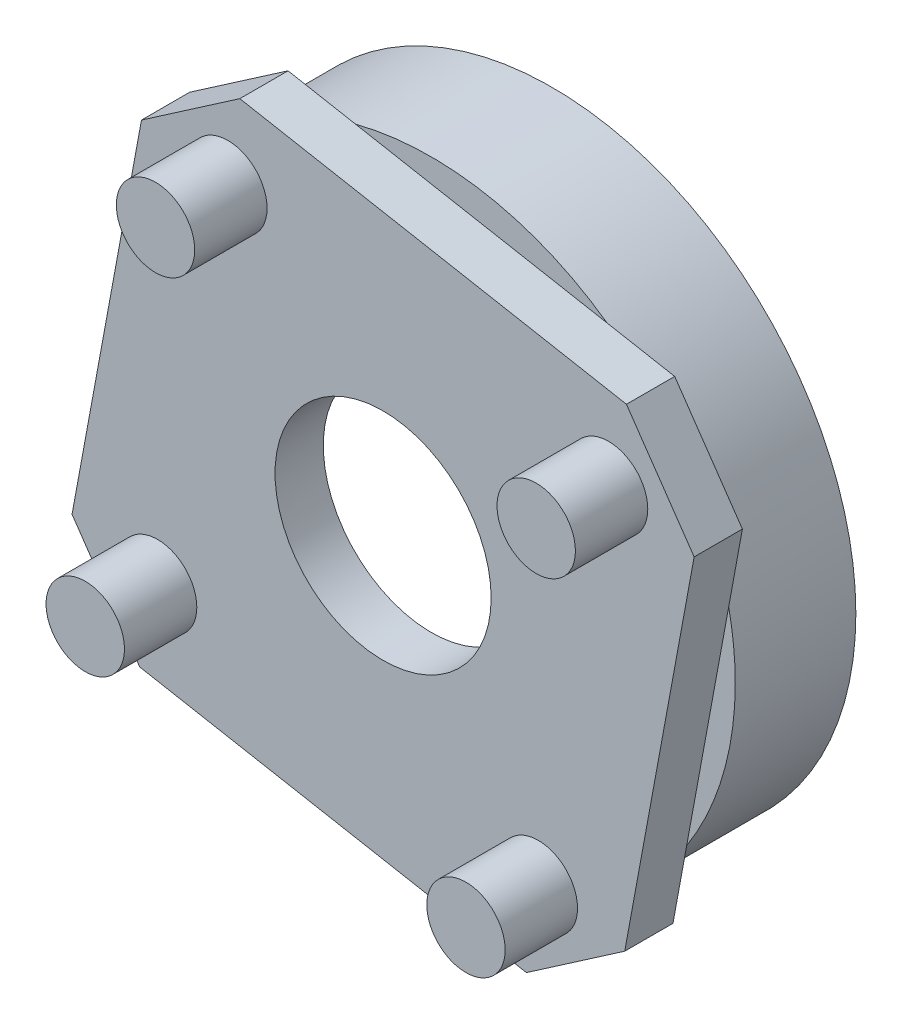
SolidWorks part; units mm, degrees
ref_plane "Front Plane" through (0, 0, 0) normal (0, 0, 1) x (1, 0, 0)
ref_plane "Top Plane" through (0, 0, 0) normal (0, 1, 0) x (1, 0, 0)
ref_plane "Right Plane" through (0, 0, 0) normal (1, 0, 0) x (0, 0, -1)
sketch "Sketch1" plane through (0, 0, 0) normal (0, 0, 1) x (1, 0, 0)
  circle A1 centre (0, 0) radius 12.6
  circle A2 centre (0, 0) radius 11.1
  circle A3 centre (0, 0) radius 11.1
  dimension "D1" = 0.1
  dimension "D2" = 1.5
extrude "Boss-Extrude1" add sketch "Sketch1" against normal blind 5
chamfer "Chamfer1" distance 1 angle 45 1 edges at (11.1, 0, -5)
sketch "Sketch2" plane through (0, 0, 0) normal (0, 0, 1) x (1, 0, 0)
  circle A0 centre (-6.4355, 9.348) radius 1.775 construction
  circle A1 centre (9.348, 6.4355) radius 1.775 construction
  circle A2 centre (6.4355, -9.348) radius 1.775 construction
  circle A3 centre (-9.348, -6.4355) radius 1.775 construction
  circle A4 centre (-6.4355, 9.348) radius 1.775 construction
  circle A6 centre (9.348, 6.4355) radius 1.775 construction
  circle A7 centre (6.4355, -9.348) radius 1.775 construction
  circle A8 centre (-9.348, -6.4355) radius 1.775 construction
  circle A9 centre (-9.348, -6.4355) radius 1.625
  circle A10 centre (6.4355, -9.348) radius 1.625
  circle A11 centre (9.348, 6.4355) radius 1.625
  circle A12 centre (-6.4355, 9.348) radius 1.625
  dimension "D1" = 0.15
extrude "Boss-Extrude2" add sketch "Sketch2" along normal blind 5
sketch "Sketch3" plane through (0, 0, 0) normal (0, 0, 1) x (1, 0, 0)
  line L0 (12.8956, 5.6843) -> (10.0888, 9.7613)
  line L1 (5.9406, -12.7191) -> (10.0176, -9.9124)
  line L2 (-12.8956, -5.6843) -> (-10.0888, -9.7613)
  line L3 (-5.9406, 12.7191) -> (-10.0176, 9.9124)
  line L5 (-10.5805, -9.6706) -> (6.4323, -12.8099)
  line L6 (9.9269, -10.4041) -> (12.9863, 6.176)
  line L7 (10.5805, 9.6706) -> (-6.4323, 12.8099)
  line L8 (-9.9269, 10.4041) -> (-12.9863, -6.176)
  line L9 (-10.0888, -9.7613) -> (5.9406, -12.7191)
  line L10 (10.0176, -9.9124) -> (12.8956, 5.6843)
  line L11 (10.0888, 9.7613) -> (-5.9406, 12.7191)
  line L12 (-10.0176, 9.9124) -> (-12.8956, -5.6843)
  arc A0 (-8.0173, 9.7202) -> (-10.9585, -6.2187) centre (0, 0) ccw construction
  arc A1 (-8.0173, 9.7202) -> (-10.9585, -6.2187) centre (0, 0) ccw
  arc A4 (6.4323, -12.8099) -> (9.9269, -10.4041) centre (6.9767, -9.8597) ccw
  arc A5 (12.9863, 6.176) -> (10.5805, 9.6706) centre (10.0361, 6.7204) ccw
  arc A6 (-6.4323, 12.8099) -> (-9.9269, 10.4041) centre (-6.9767, 9.8597) ccw
  arc A7 (-12.9863, -6.176) -> (-10.5805, -9.6706) centre (-10.0361, -6.7204) ccw
  arc A12 (-9.7202, -8.0173) -> (6.2187, -10.9585) centre (0, 0) ccw
  arc A13 (4.9252, -9.9475) -> (6.2187, -10.9585) centre (6.4355, -9.348) ccw
  arc A14 (-8.151, -7.5346) -> (4.9252, -9.9475) centre (0, 0) ccw
  arc A15 (-9.7202, -8.0173) -> (-8.151, -7.5346) centre (-9.348, -6.4355) ccw
  arc A16 (-9.7202, -8.0173) -> (6.2187, -10.9585) centre (0, 0) ccw
  arc A17 (4.9252, -9.9475) -> (6.2187, -10.9585) centre (6.4355, -9.348) ccw
  arc A18 (-8.151, -7.5346) -> (4.9252, -9.9475) centre (0, 0) ccw
  arc A19 (-9.7202, -8.0173) -> (-8.151, -7.5346) centre (-9.348, -6.4355) ccw
  arc A22 (-7.5346, 8.151) -> (-9.9475, -4.9252) centre (0, 0) ccw
  arc A23 (-8.0173, 9.7202) -> (-7.5346, 8.151) centre (-6.4355, 9.348) ccw
  arc A24 (-8.0173, 9.7202) -> (-10.9585, -6.2187) centre (0, 0) ccw
  arc A25 (-9.9475, -4.9252) -> (-10.9585, -6.2187) centre (-9.348, -6.4355) ccw
  arc A26 (-7.5346, 8.151) -> (-9.9475, -4.9252) centre (0, 0) ccw
  arc A27 (-8.0173, 9.7202) -> (-7.5346, 8.151) centre (-6.4355, 9.348) ccw
  arc A28 (-8.0173, 9.7202) -> (-10.9585, -6.2187) centre (0, 0) ccw
  arc A29 (-9.9475, -4.9252) -> (-10.9585, -6.2187) centre (-9.348, -6.4355) ccw
  arc A30 (9.7202, 8.0173) -> (-6.2187, 10.9585) centre (0, 0) ccw
  arc A31 (-4.9252, 9.9475) -> (-6.2187, 10.9585) centre (-6.4355, 9.348) ccw
  arc A32 (8.151, 7.5346) -> (-4.9252, 9.9475) centre (0, 0) ccw
  arc A33 (9.7202, 8.0173) -> (8.151, 7.5346) centre (9.348, 6.4355) ccw
  arc A34 (9.7202, 8.0173) -> (-6.2187, 10.9585) centre (0, 0) ccw
  arc A35 (-4.9252, 9.9475) -> (-6.2187, 10.9585) centre (-6.4355, 9.348) ccw
  arc A36 (8.151, 7.5346) -> (-4.9252, 9.9475) centre (0, 0) ccw
  arc A37 (9.7202, 8.0173) -> (8.151, 7.5346) centre (9.348, 6.4355) ccw
  arc A38 (8.0173, -9.7202) -> (10.9585, 6.2187) centre (0, 0) ccw
  arc A39 (9.9475, 4.9252) -> (10.9585, 6.2187) centre (9.348, 6.4355) ccw
  arc A40 (7.5346, -8.151) -> (9.9475, 4.9252) centre (0, 0) ccw
  arc A41 (8.0173, -9.7202) -> (7.5346, -8.151) centre (6.4355, -9.348) ccw
  arc A42 (8.0173, -9.7202) -> (10.9585, 6.2187) centre (0, 0) ccw
  arc A43 (9.9475, 4.9252) -> (10.9585, 6.2187) centre (9.348, 6.4355) ccw
  arc A44 (7.5346, -8.151) -> (9.9475, 4.9252) centre (0, 0) ccw
  arc A45 (8.0173, -9.7202) -> (7.5346, -8.151) centre (6.4355, -9.348) ccw
  point P0 (-13.5307, -9.1262)
  point P44 (-9.3825, 13.3543)
  point P47 (13.5307, 9.1262)
  point P51 (9.3825, -13.3543)
  arc M25 (9.7202, 8.0173) -> (-6.2187, 10.9585) centre (0, 0) ccw
  arc M26 (-6.2187, 10.9585) -> (-4.9252, 9.9475) centre (-6.4355, 9.348) cw
  arc M27 (-4.9252, 9.9475) -> (8.151, 7.5346) centre (0, 0) cw
  arc M28 (8.151, 7.5346) -> (9.7202, 8.0173) centre (9.348, 6.4355) cw
  dimension "D1" = 0
  dimension "D2" = 0
  dimension "D3" = 0
  dimension "D4" = 0
  dimension "D5" = 0
extrude "Boss-Extrude3" add sketch "Sketch3" along normal blind 1 contours A42 A45 A44 A43 L10 L11 L12 A1 A27 A26 A29 L9 A16 A19 A18 A17 M25 M28 M27 M26 | A19 A16 L9 A17 A18 | A45 A42 L10 A43 A44 | L11 M25 M26 M27 M28 | A29 A26 A27 A1 L12 region at (0, 0, 0) region at (11.2929, -2.0838, 0) region at (8.466, 9.1065, 0) region at (-2.044, -11.0769, 0) region at (-9.2884, 8.2655, 0)
sketch "Sketch4" plane through (0, 0, 1) normal (0, 0, 1) x (1, 0, 0)
  line L0 (-6.4355, 9.348) -> (-10.6582, 6.441)
  line L1 (-6.4355, 9.348) -> (6.4355, -9.348) construction
  line L2 (-6.4355, 9.348) -> (-2.4692, 12.0786)
  line L3 (9.348, 6.4355) -> (6.6174, 10.4019)
  line L4 (10.0176, -9.9124) -> (12.8956, 5.6843)
  line L5 (10.0888, 9.7613) -> (-5.9406, 12.7191)
  line L6 (-10.0176, 9.9124) -> (-12.8956, -5.6843)
  line L7 (-10.0888, -9.7613) -> (5.9406, -12.7191)
  line L8 (10.0176, -9.9124) -> (12.8956, 5.6843)
  line L9 (10.0888, 9.7613) -> (-5.9406, 12.7191)
  line L10 (-10.0176, 9.9124) -> (-12.8956, -5.6843)
  line L11 (-10.0888, -9.7613) -> (5.9406, -12.7191)
  line L12 (9.348, 6.4355) -> (12.255, 2.2129)
  line L13 (6.4355, -9.348) -> (10.6582, -6.441)
  line L14 (6.4355, -9.348) -> (2.4692, -12.0786)
  line L15 (-9.348, -6.4355) -> (-6.6174, -10.4019)
  line L16 (-9.348, -6.4355) -> (-12.255, -2.2129)
  line L17 (9.348, 6.4355) -> (-9.348, -6.4355) construction
  line L26 (5.9406, -12.7191) -> (10.0176, -9.9124)
  line L27 (5.9406, -12.7191) -> (10.0176, -9.9124)
  line L28 (12.8956, 5.6843) -> (10.0888, 9.7613)
  line L29 (12.8956, 5.6843) -> (10.0888, 9.7613)
  line L30 (-5.9406, 12.7191) -> (-10.0176, 9.9124)
  line L31 (-5.9406, 12.7191) -> (-10.0176, 9.9124)
  line L32 (-12.8956, -5.6843) -> (-10.0888, -9.7613)
  line L33 (-12.8956, -5.6843) -> (-10.0888, -9.7613)
  circle A0 centre (6.4355, -9.348) radius 1.625 construction
  circle A1 centre (-9.348, -6.4355) radius 1.625 construction
  circle A2 centre (9.348, 6.4355) radius 1.625 construction
  circle A3 centre (-6.4355, 9.348) radius 1.625 construction
  circle A12 centre (6.4355, -9.348) radius 1.625
  circle A13 centre (-9.348, -6.4355) radius 1.625
  circle A14 centre (9.348, 6.4355) radius 1.625
  circle A15 centre (-6.4355, 9.348) radius 1.625
  circle M17 centre (-9.348, -6.4355) radius 1.625
  circle M18 centre (6.4355, -9.348) radius 1.625
  circle M19 centre (9.348, 6.4355) radius 1.625
  circle M20 centre (-6.4355, 9.348) radius 1.625
  line M22 (10.0176, -9.9124) -> (12.8956, 5.6843)
  line M24 (10.0888, 9.7613) -> (-5.9406, 12.7191)
  line M26 (-10.0176, 9.9124) -> (-12.8956, -5.6843)
  line M28 (-10.0888, -9.7613) -> (5.9406, -12.7191)
  dimension "D2" = 90
  dimension "D3" = 90
  dimension "D4" = 90
  dimension "D5" = 90
  dimension "D1" = 0
extrude "Boss-Extrude4" add sketch "Sketch4" along normal blind 1 contours L2 L0 M20 M24 M26 | L16 L10 L15 M17 M28 | L14 L11 L13 M18 M22 | L12 L8 L3 M19 M24 | L16 L15 L11 L14 L13 L8 L12 L3 L2 L0 M17 M18 M19 M24 M20 M26 region at (0, 0, 1) region at (-9.2746, 7.5187, 1) region at (-11.3472, -3.7135, 1) region at (8.3344, 9.9801, 1) region at (3.8416, -11.259, 1)
sketch "Sketch5" plane through (0, 0, 0) normal (0, 0, 1) x (1, 0, 0)
  line L5 (9.348, 6.4355) -> (-9.348, -6.4355) construction
  circle A0 centre (0, 0) radius 4.4802
  point P0 (0, 0)
extrude "Cut-Extrude1" cut sketch "Sketch5" along normal through all
